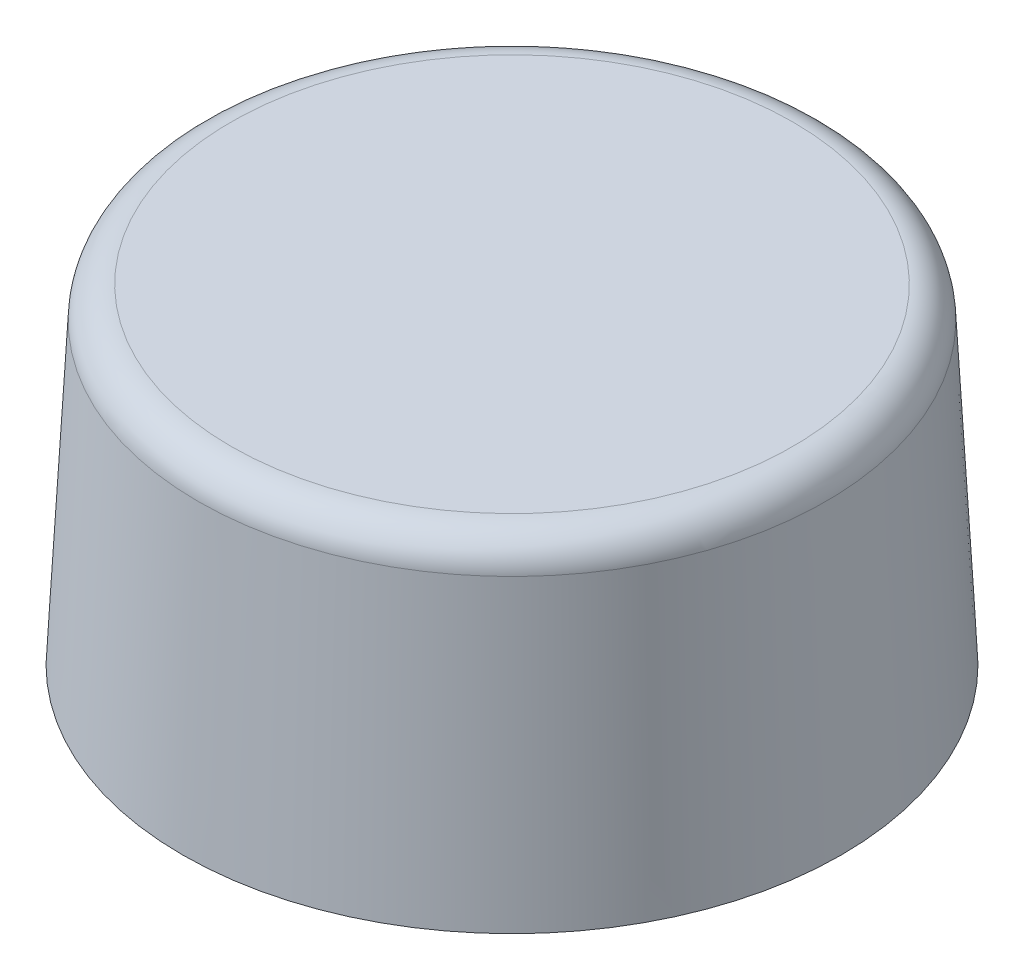
SolidWorks part; units mm, degrees
material "SANTOPRENE"
ref_plane "Front Plane" through (0, 0, 0) normal (0, 0, 1) x (1, 0, 0)
ref_plane "Top Plane" through (0, 0, 0) normal (0, 1, 0) x (1, 0, 0)
ref_plane "Right Plane" through (0, 0, 0) normal (1, 0, 0) x (0, 0, -1)
sketch "Sketch1" plane through (0, 0, 0) normal (0, 1, 0) x (1, 0, 0)
  circle A0 centre (0, 0) radius 10
  dimension "D1" = 20
extrude "Boss-Extrude1" add sketch "Sketch1" along normal blind 10 draft 3
dome "Dome1" faces to dome 1 distance 3 reverse direction no elliptical dome no face at (0, 0, 10) parameters "D1"=3
fillet "Fillet1" radius 1 1 edges at (0, 10, 9.4759)
